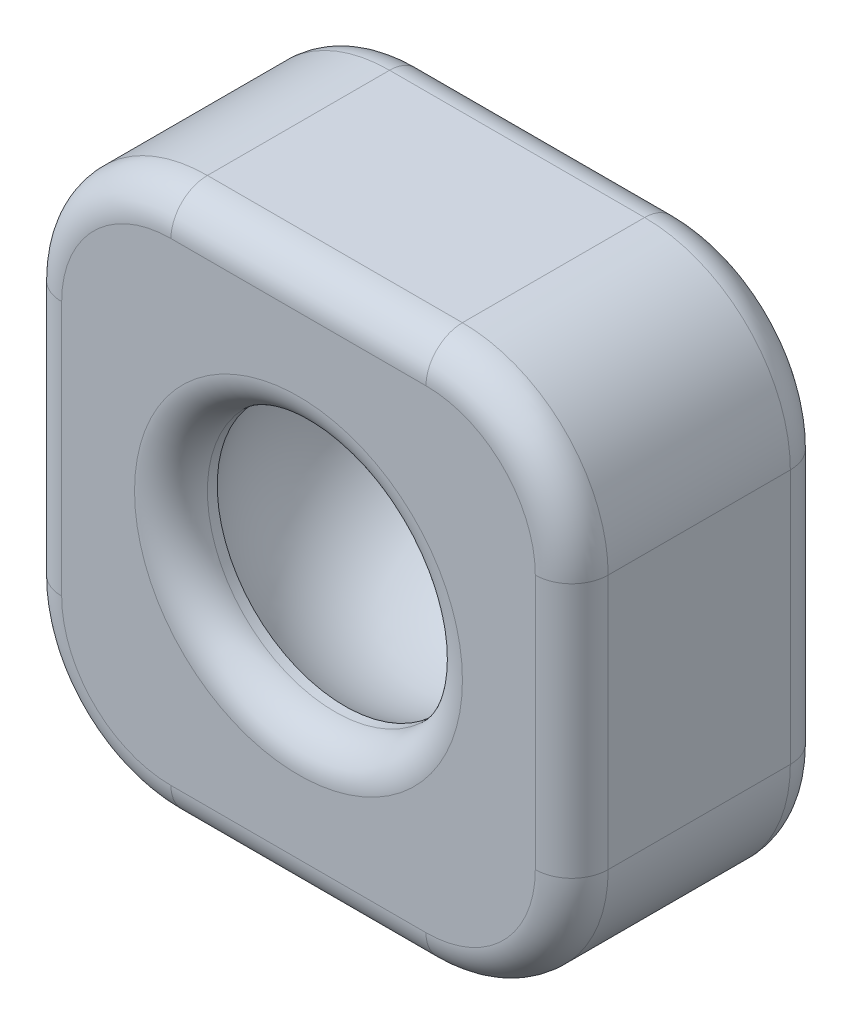
SolidWorks part; units mm, degrees
material "PLA_Rotula_Chica"
ref_plane "Front Plane" through (0, 0, 0) normal (0, 0, 1) x (1, 0, 0)
ref_plane "Top Plane" through (0, 0, 0) normal (0, 1, 0) x (1, 0, 0)
ref_plane "Right Plane" through (0, 0, 0) normal (1, 0, 0) x (0, 0, -1)
ref_plane "Plane1" through (0, 0, 5) normal (0, 0, 1) x (1, 0, 0)
sketch "Sketch1" plane through (0, 0, 5) normal (0, 0, 1) x (1, 0, 0)
  line L0 (-7.5, -7.5) -> (7.5, -7.5)
  line L1 (7.5, -7.5) -> (7.5, 7.5)
  line L2 (7.5, 7.5) -> (-7.5, 7.5)
  line L3 (-7.5, 7.5) -> (-7.5, -7.5)
  line L4 (-7.5, 7.5) -> (7.5, -7.5) construction
  line L5 (7.5, 7.5) -> (-7.5, -7.5) construction
  circle A0 centre (0, 0) radius 3.5
  dimension "D3" = 7
  dimension "D1" = 15
  dimension "D2" = 15
extrude "Boss-Extrude1" add sketch "Sketch1" against normal blind 3.5 and the other way blind 3.5
sketch "Sketch2" plane through (0, 0, 0) normal (0, 1, 0) x (1, 0, 0)
  line L0 (3.5, -2.7701) -> (3.5, -7.2299)
  line L1 (0, -1.5) -> (0, -8.5) construction
  line L2 (-55, -5) -> (55, -5) construction
  line L3 (3.5, -1.5) -> (-3.5, -1.5) construction
  line L4 (-3.5, -8.5) -> (3.5, -8.5) construction
  arc A0 (3.5, -7.2299) -> (3.5, -2.7701) centre (0, -5) ccw
  dimension "D1" = 4.15
  dimension "D2" = 3.5
revolve "Cut-Revolve1" cut sketch "Sketch2" angle 360 about L1 reverse direction yes
fillet "Fillet1" radius 4 4 edges at (-7.5, 7.5, 5) (-7.5, -7.5, 5) (7.5, 7.5, 5) (7.5, -7.5, 5) tangent propagation no
fillet "Fillet2" radius 1 18 edges at (-3.5, 0, 8.5) (-6.3284, -6.3284, 8.5) (-7.5, 0, 8.5) (-6.3284, 6.3284, 8.5) (0, 7.5, 8.5) (6.3284, 6.3284, 8.5) (7.5, 0, 8.5) (6.3284, -6.3284, 8.5) (0, -7.5, 8.5) (6.3284, 6.3284, 1.5) (0, 7.5, 1.5) (-6.3284, 6.3284, 1.5) (-7.5, 0, 1.5) (-6.3284, -6.3284, 1.5) (0, -7.5, 1.5) (6.3284, -6.3284, 1.5) (7.5, 0, 1.5) (-3.5, 0, 1.5)
